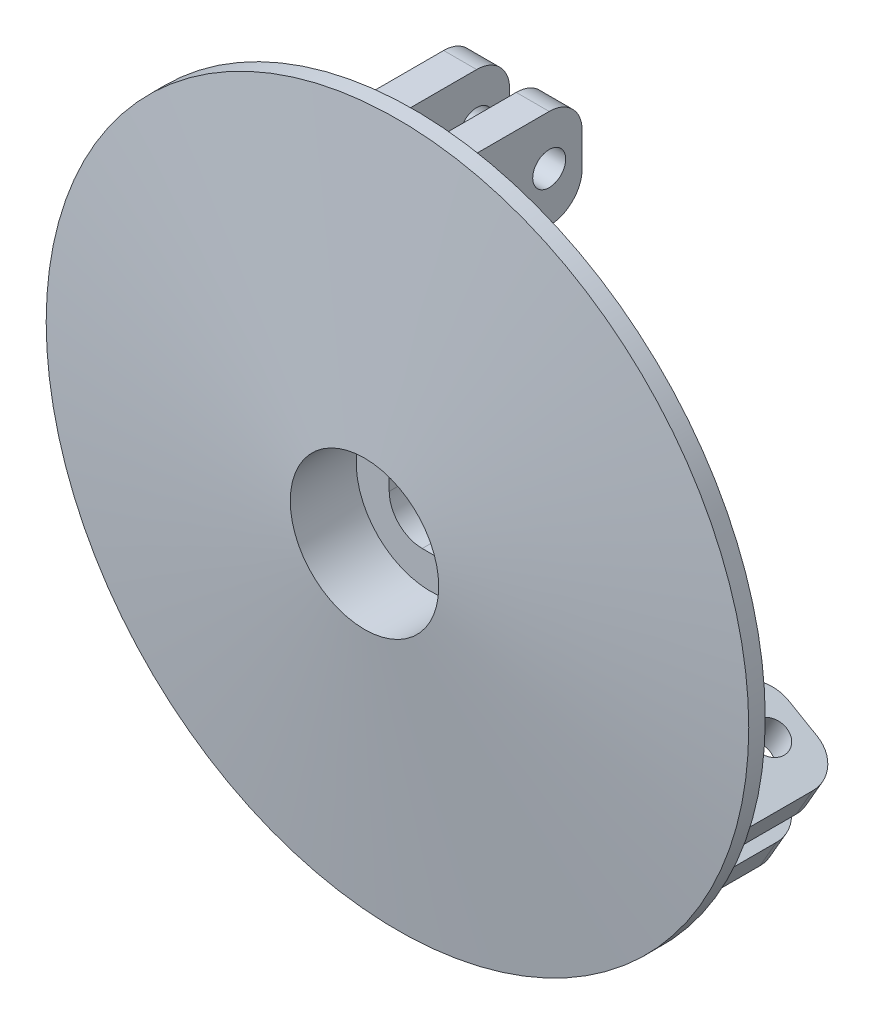
SolidWorks part; units mm, degrees
material "7075-T6 (SN)"
ref_plane "Front Plane" through (0, 0, 0) normal (0, 0, 1) x (1, 0, 0)
ref_plane "Top Plane" through (0, 0, 0) normal (0, 1, 0) x (1, 0, 0)
ref_plane "Right Plane" through (0, 0, 0) normal (1, 0, 0) x (0, 0, -1)
sketch "Sketch1" plane through (0, 0, 0) normal (0, 0, 1) x (1, 0, 0)
  circle A0 centre (0, 0) radius 22.5
  dimension "D1" = 45
extrude "Boss-Extrude1" add sketch "Sketch1" along normal blind 15
sketch "Sketch3" plane through (0, 0, 0) normal (1, 0, 0) x (0, 0, -1)
  line L0 (-15, 22.5) -> (-5, 106.5)
  line L1 (-5, 106.5) -> (0, 106.5)
  line L2 (0, 106.5) -> (0, 106.2034)
  line L3 (0, 22.5) -> (-15, 22.5)
  line L4 (-9.9647, 22.5) -> (0, 106.2034)
  line L5 (-10.0351, 21.9089) -> (-0.0351, 105.9089) construction
  dimension "D1" = 5
  dimension "D2" = 106.5
  dimension "D3" = 5
ref_axis "Axis1" through (0, 0, 15) along (0, 0, -1)
revolve "Revolve1" add sketch "Sketch3" angle 360 about axis through (0, 0, 15) along (0, 0, -1) region at (0, 64.4995, 7.4824)
sketch "Sketch4" plane through (0, 0, 0) normal (0, 0, -1) x (-1, 0, 0)
  line L1 (-2.5, 12.5) -> (2.5, 12.5)
  line L2 (-12.5, 2.5) -> (-12.5, -2.5)
  line L3 (-2.5, -12.5) -> (2.5, -12.5)
  line L4 (12.5, 2.5) -> (12.5, -2.5)
  line L5 (-12.5, 12.5) -> (12.5, -12.5) construction
  line L6 (-12.5, -12.5) -> (12.5, 12.5) construction
  circle A0 centre (0, 0) radius 25
  arc A1 (-12.5, -2.5) -> (-2.5, -12.5) centre (-2.5, -2.5) ccw
  arc A2 (2.5, -12.5) -> (12.5, -2.5) centre (2.5, -2.5) ccw
  arc A3 (2.5, 12.5) -> (12.5, 2.5) centre (2.5, 2.5) cw
  arc A4 (-2.5, 12.5) -> (-12.5, 2.5) centre (-2.5, 2.5) ccw
  dimension "D1" = 50
  dimension "D4" = 10
  dimension "D2" = 25
  dimension "D3" = 25
extrude "Boss-Extrude2" add sketch "Sketch4" along normal blind 30 and the other way blind 10
extrude "Cut-Extrude1" cut sketch "Sketch1<3>" against normal blind 5
sketch "Sketch1<3>" plane through (0, 0, 0) normal (0, 0, 1) x (1, 0, 0) same geometry as "Sketch1"
extrude "Cut-Extrude2" cut sketch "Sketch1<4>" along normal blind 15
sketch "Sketch1<4>" plane through (0, 0, 0) normal (0, 0, 1) x (1, 0, 0) same geometry as "Sketch1"
sketch "Sketch10" plane through (0, 0, -5) normal (0, 0, 1) x (1, 0, 0)
  line L0 (0, 106.5) -> (0, 101.5) construction
  line L1 (-16, 101.5) -> (16, 101.5) construction
  line L3 (-16, 101.5) -> (-6, 101.5)
  line L4 (-16, 101.5) -> (-16, 71.5)
  line L5 (-16, 71.5) -> (-6, 71.5)
  line L6 (-6, 101.5) -> (-6, 71.5)
  line L7 (16, 101.5) -> (6, 101.5)
  line L8 (16, 101.5) -> (16, 71.5)
  line L9 (16, 71.5) -> (6, 71.5)
  line L10 (6, 101.5) -> (6, 71.5)
  circle A0 centre (0, 0) radius 106.5 construction
  point P9 (0, 101.5)
  dimension "D1" = 32
  dimension "D2" = 5
  dimension "D3" = 30
  dimension "D4" = 10
  dimension "D5" = 10
  dimension "D6" = 30
extrude "Boss-Extrude3" add sketch "Sketch10" against normal blind 30 and the other way up to surface
fillet "Fillet1" radius 10 4 edges at (-11, 71.5, -35) (11, 71.5, -35) (11, 101.5, -35) (-11, 101.5, -35)
sketch "Sketch11" plane through (-16, 0, 0) normal (-1, 0, 0) x (0, 0, 1)
  line L0 (-25, 86.5) -> (-35, 86.5) construction
  line L1 (-35, 91.5) -> (-35, 81.5) construction
  circle A0 centre (-25, 86.5) radius 5
  dimension "D1" = 10
  dimension "D2" = 10
extrude "Cut-Extrude3" cut sketch "Sketch11" against normal up to surface (32 mm away) up to face at (16, 84, -19.6759)
pattern_circular "CirPattern1" count 3 over 360 about axis through (0, 0, 0) along (0, 0, 1) of "Cut-Extrude3", "Fillet1", "Boss-Extrude3"
fillet "Fillet2" radius 10 1 edges at (-25, 0, -30)
